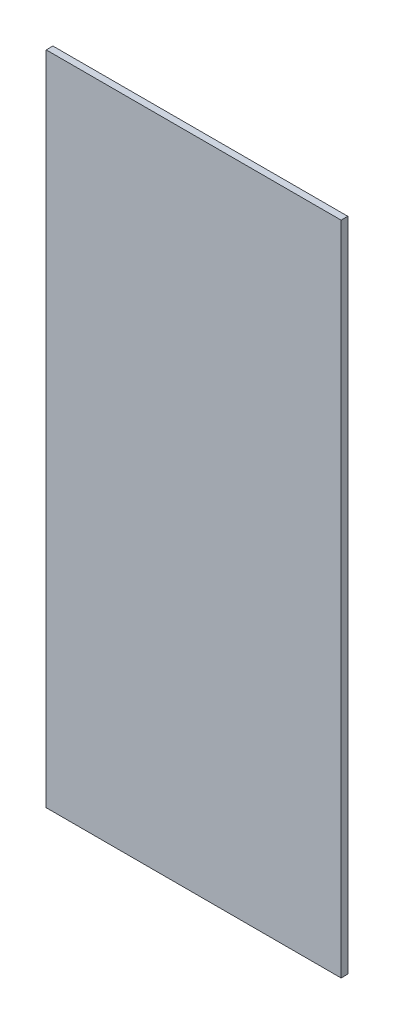
SolidWorks part; units mm, degrees
ref_plane "Спереди" through (0, 0, 0) normal (0, 0, 1) x (1, 0, 0)
ref_plane "Сверху" through (0, 0, 0) normal (0, 1, 0) x (1, 0, 0)
ref_plane "Справа" through (0, 0, 0) normal (1, 0, 0) x (0, 0, -1)
sketch "Sketch1" plane through (0, 0, 0) normal (0, 0, 1) x (1, 0, 0)
  line L0 (88.2, 0) -> (88.2, -392.6) construction
  line L1 (-88.2, 0) -> (88.2, 0)
  line L2 (-88.2, 0) -> (-88.2, -392.6)
  line L3 (-88.2, -392.6) -> (88.2, -392.6)
  line L4 (88.2, 0) -> (88.2, -392.6)
  line L7 (88.2, -392.6) -> (84.2, -392.6) construction
  point P4 (0, -392.6)
  point P5 (0, 0)
extrude "Extrude1" add sketch "Sketch1" along normal blind 4
equation "\"thickness\"=4"
equation "\"D1@Extrude1\"=\"thickness\""
equation "\"pin_l\"=5"
equation "\"pin_skew\"=4"
equation "\"pin_r\"=5"
equation "\"M4_plastic_thread\"=3.8"
equation "\"M3_plastic_thread\" = 2.8"
